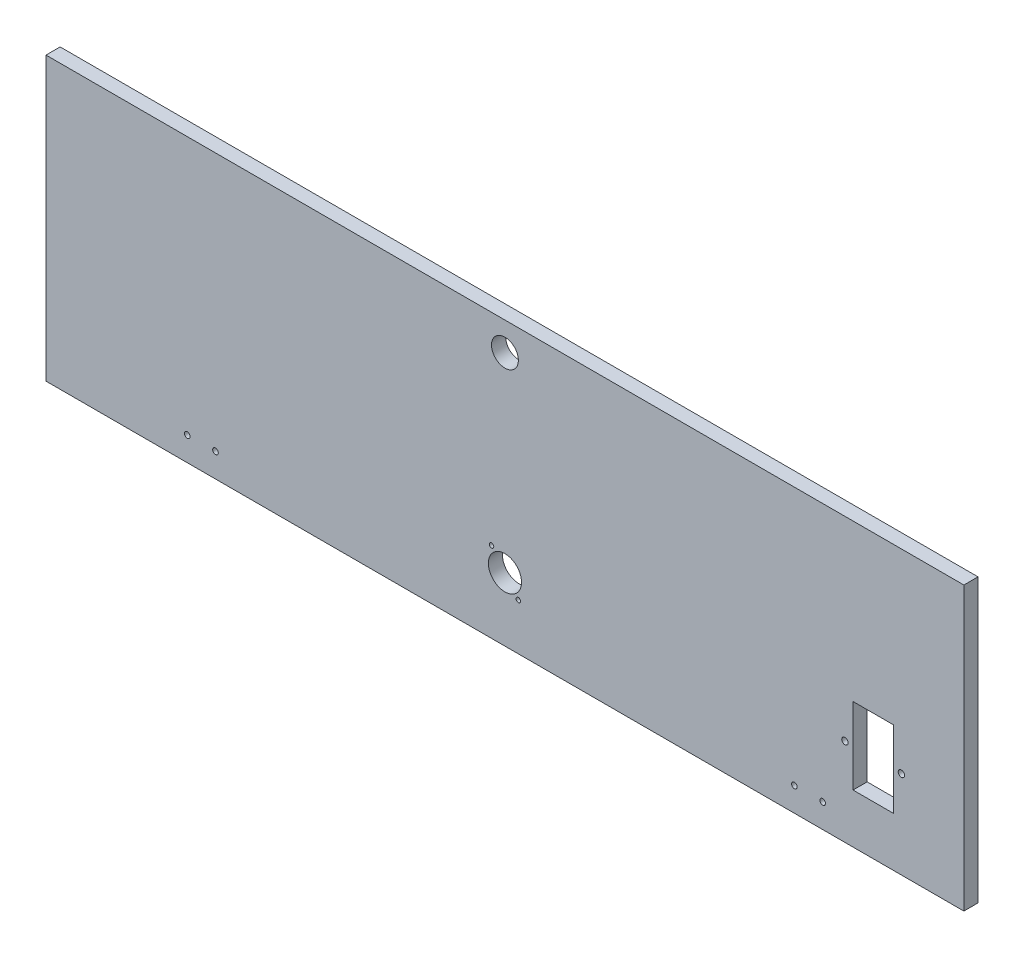
SolidWorks part; units mm, degrees
ref_plane "Plan de face" through (0, 0, 0) normal (0, 0, 1) x (1, 0, 0)
ref_plane "Plan de dessus" through (0, 0, 0) normal (0, 1, 0) x (1, 0, 0)
ref_plane "Plan de droite" through (0, 0, 0) normal (1, 0, 0) x (0, 0, -1)
sketch "Esquisse1" plane through (0, 0, 0) normal (0, 0, 1) x (1, 0, 0)
  line L1 (0, 0) -> (650, 0)
  line L2 (0, 0) -> (0, 200)
  line L3 (0, 200) -> (650, 200)
  line L4 (650, 0) -> (650, 200)
  dimension "D1" = 200
  dimension "D2" = 650
extrude "Boss.-Extru.1" add sketch "Esquisse1" along normal blind 10
sketch "Esquisse2" plane through (0, 0, 10) normal (0, 0, 1) x (1, 0, 0)
  line L4 (0, 200) -> (0, 0) construction
  line L5 (650, 0) -> (650, 200) construction
  line L6 (0, 0) -> (650, 0) construction
  circle A0 centre (100, 17) radius 2
  circle A1 centre (120, 17) radius 2
  circle A2 centre (530, 17) radius 2
  circle A3 centre (550, 17) radius 2
  dimension "D1" = 4
  dimension "D2" = 4
  dimension "D3" = 4
  dimension "D4" = 4
  dimension "D5" = 20
  dimension "D6" = 20
  dimension "D7" = 100
  dimension "D8" = 100
  dimension "D9" = 17
  dimension "D10" = 17
  dimension "D11" = 17
  dimension "D12" = 17
extrude "Enlèv. mat.-Extru.1" cut sketch "Esquisse2" against normal blind 10
sketch "Esquisse3" plane through (0, 0, 10) normal (0, 0, 1) x (1, 0, 0)
  line L0 (0, 0) -> (650, 0) construction
  line L1 (334.5004, 33.0006) -> (325, 45)
  line L2 (325, 45) -> (315.4996, 56.9994)
  line L3 (325, 45) -> (265.8175, 45)
  line L4 (325, 45) -> (364.3682, 45)
  line L5 (650, 0) -> (650, 200) construction
  line L6 (571.5, 35) -> (600, 35)
  line L7 (571.5, 35) -> (571.5, 89.3)
  line L8 (571.5, 89.3) -> (600, 89.3)
  line L9 (600, 35) -> (600, 89.3)
  circle A0 centre (325, 45) radius 11.75
  circle A1 centre (315.4996, 56.9994) radius 1.6
  circle A2 centre (334.5004, 33.0006) radius 1.6
  circle A3 centre (565.75, 62.15) radius 2.25
  circle A4 centre (605.75, 62.15) radius 2.25
  point P4 (325, 0)
  point P19 (585.75, 89.3)
  point P20 (571.5, 62.15)
  point P21 (0, 0)
  dimension "D1" = 23.5
  dimension "D4" = 3.2
  dimension "D5" = 3.2
  dimension "D14" = 4.5
  dimension "D15" = 4.5
  dimension "D2" = 0
  dimension "D3" = 45
  dimension "D6" = 30.61
  dimension "D7" = 15.305
  dimension "D8" = 51.63
  dimension "D9" = 180
  dimension "D10" = 51.63
  dimension "D11" = 15.305
  dimension "D12" = 28.5
  dimension "D13" = 54.3
  dimension "D16" = 40
  dimension "D17" = 20
  dimension "D18" = 0
  dimension "D19" = 35
  dimension "D20" = 50
  dimension "D21" = 20
extrude "Enlèv. mat.-Extru.2" cut sketch "Esquisse3" against normal blind 10 contours L3 A0 L1 | L4 A0 L2 | L1 A0 L4 | L2 A0 L3 | A1 | A2 | L6 L9 L8 L7 | A3 | A4 region at (314.1, 57.6764, 10) region at (322.2589, 39.3335, 10) region at (331.8154, 41.7031, 10) region at (335.1774, 34.4002, 10) region at (318.1846, 48.2969, 10) region at (327.7411, 50.6665, 10) region at (585.75, 62.15, 10)
sketch "Esquisse4" plane through (0, 0, 10) normal (0, 0, 1) x (1, 0, 0)
  line L0 (650, 200) -> (0, 200) construction
  circle A0 centre (325, 180) radius 9.5
  point P4 (325, 200)
  point P7 (0, 0)
  dimension "D1" = 19
  dimension "D3" = 20
  dimension "D2" = 0
extrude "Enlèv. mat.-Extru.3" cut sketch "Esquisse4" against normal blind 10
sketch "Esquisse5" plane through (0, 0, 0) normal (0, 0, 1) x (1, 0, 0)
  line L0 (650, 200) -> (0, 200) construction
  circle A0 centre (341, 180) radius 1.5
  circle A1 centre (309, 180) radius 1.5
  point P6 (325, 200)
  dimension "D2" = 3
  dimension "D3" = 3
  dimension "D1" = 32
  dimension "D4" = 16
  dimension "D5" = 20
  dimension "D6" = 20
extrude "Enlèv. mat.-Extru.4" cut sketch "Esquisse5" along normal blind 2
